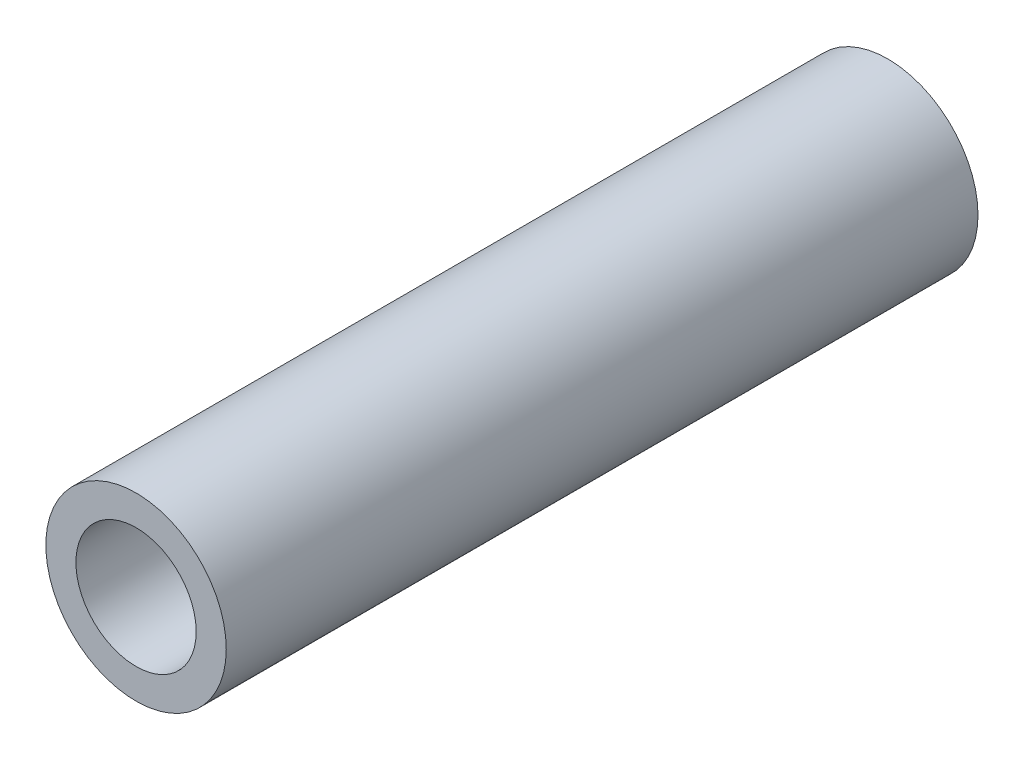
SolidWorks part; units mm, degrees
ref_plane "Front Plane" through (0, 0, 0) normal (0, 0, 1) x (1, 0, 0)
ref_plane "Top Plane" through (0, 0, 0) normal (0, 1, 0) x (1, 0, 0)
ref_plane "Right Plane" through (0, 0, 0) normal (1, 0, 0) x (0, 0, -1)
sketch "Real Length Sketch" plane through (0, 0, 0) normal (1, 0, 0) x (0, 0, -1)
  point P0 (0, 0)
  point P1 (25, 0)
  dimension "Length" = 25
sketch "Cross Section Sketch" plane through (0, 0, 0) normal (0, 0, 1) x (1, 0, 0)
  circle A0 centre (0, 0) radius 3
  circle A1 centre (0, 0) radius 2
  dimension "OD" = 6
  dimension "ID" = 4
extrude "Extrude Length" add sketch "Cross Section Sketch" along normal mid plane 25
